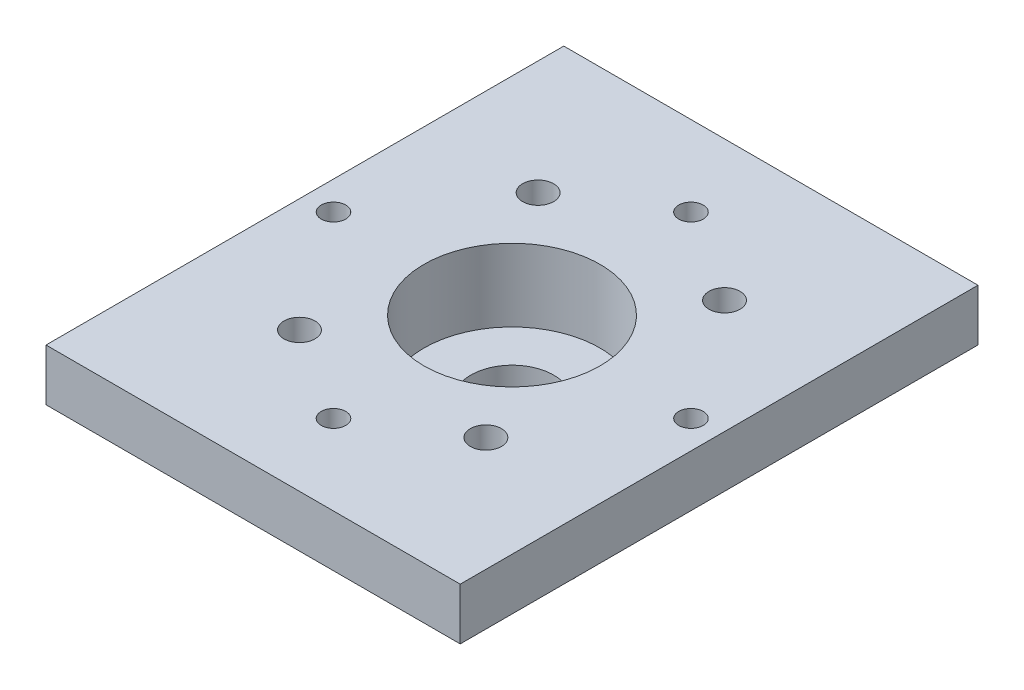
SolidWorks part; units mm, degrees
ref_plane "Front Plane" through (0, 0, 0) normal (0, 0, 1) x (1, 0, 0)
ref_plane "Top Plane" through (0, 0, 0) normal (0, 1, 0) x (1, 0, 0)
ref_plane "Right Plane" through (0, 0, 0) normal (1, 0, 0) x (0, 0, -1)
sketch "Sketch1" plane through (0, 0, 0) normal (0, 1, 0) x (1, 0, 0)
  line L0 (25.7342, 28.651) -> (-19.9858, -29.769) construction
  line L1 (-19.9858, 28.651) -> (25.7342, 28.651)
  line L2 (-19.9858, 28.651) -> (-19.9858, -29.769)
  line L3 (-19.9858, -29.769) -> (25.7342, -29.769)
  line L4 (25.7342, 28.651) -> (25.7342, -29.769)
  point P4 (2.8742, -0.559)
  point P5 (0, 0)
  dimension "D1" = 58.42
  dimension "D2" = 45.72
extrude "Boss-Extrude1" add sketch "Sketch1" along normal blind 6.35
sketch "Sketch2" plane through (0, 6.35, 0) normal (0, 1, 0) x (1, 0, 0)
  line L1 (25.7342, 28.651) -> (-19.9858, 28.651) construction
  line L3 (-19.9858, -0.559) -> (25.7342, -0.559) construction
  line L4 (-19.9858, 28.651) -> (-19.9858, -29.769) construction
  line L5 (25.7342, -29.769) -> (25.7342, 28.651) construction
  line L9 (-19.9858, -0.559) -> (2.8742, 28.651) construction
  line L10 (2.8742, 28.651) -> (25.7342, -0.559) construction
  circle A0 centre (-8.5558, 14.046) radius 1.905
  circle A1 centre (14.3042, 14.046) radius 1.905
  circle A2 centre (-8.6123, -15.164) radius 1.905
  circle A3 centre (14.2477, -15.164) radius 1.905
  dimension "D2" = 3.81
  dimension "D3" = 3.81
  dimension "D4" = 3.81
  dimension "D5" = 3.81
  dimension "D1" = 18.5459
  dimension "D6" = 29.21
  dimension "D7" = 29.21
  dimension "D8" = 22.86
  dimension "D9" = 22.86
sketch "Sketch3" plane through (0, 0, 0) normal (0, -1, 0) x (1, 0, 0)
  line L1 (-15.4979, 23.6108) -> (21.2464, 23.6108)
  line L2 (-15.4979, 23.6108) -> (-15.4979, -22.4927)
  line L3 (-15.4979, -22.4927) -> (21.2464, -22.4927)
  line L4 (21.2464, 23.6108) -> (21.2464, -22.4927)
  dimension "D1" = 7.62
  dimension "D2" = 7.62
extrude "Cut-Extrude1" cut sketch "Sketch2" against normal through all
extrude "Boss-Extrude2" add sketch "Sketch3" along normal blind 5.08
sketch "Sketch4" plane through (0, -5.08, 0) normal (0, -1, 0) x (1, 0, 0)
  line L0 (-19.9858, 0.559) -> (25.7342, 0.559) construction
  line L1 (-19.9858, -28.651) -> (-19.9858, 29.769) construction
  line L2 (25.7342, 29.769) -> (25.7342, -28.651) construction
  line L3 (2.8742, 29.769) -> (2.8742, -28.651) construction
  line L4 (-19.9858, 29.769) -> (25.7342, 29.769) construction
  line L5 (25.7342, -28.651) -> (-19.9858, -28.651) construction
  circle A0 centre (2.8742, 0.559) radius 7.62
  circle A1 centre (2.8742, 0.559) radius 5.08
  dimension "D1" = 10.16
  dimension "D2" = 15.24
extrude "Boss-Extrude3" add sketch "Sketch4" along normal blind 12.7
fillet "Fillet1" radius 2.54 4 edges at (25.7342, 3.175, -28.651) (-19.9858, 3.175, -28.651) (-19.9858, 3.175, 29.769) (25.7342, 3.175, 29.769)
sketch "Sketch5" plane through (0, 6.35, 0) normal (0, 1, 0) x (1, 0, 0)
  line L0 (-8.5558, 14.046) -> (14.2477, -15.164) construction
  circle A0 centre (2.846, -0.559) radius 10.795
  point P7 (2.846, -0.559)
  dimension "D1" = 21.59
extrude "Cut-Extrude2" cut sketch "Sketch5" against normal blind 8.89
extrude "Cut-Extrude4" cut sketch "Sketch4<2>" against normal blind 19.05 contours A1 region at (2.8742, -5.08, 0.559)
sketch "Sketch4<2>" plane through (0, -5.08, 0) normal (0, -1, 0) x (1, 0, 0) same geometry as "Sketch4"
sketch "Sketch6" plane through (0, 6.35, 0) normal (0, 1, 0) x (1, 0, 0)
  line L1 (28.246, 31.191) -> (-22.554, 31.191)
  line L2 (28.246, 31.191) -> (28.246, -32.309)
  line L3 (28.246, -32.309) -> (-22.554, -32.309)
  line L4 (-22.554, 31.191) -> (-22.554, -32.309)
  line L5 (28.246, 31.191) -> (-22.554, -32.309) construction
  line L6 (28.246, -32.309) -> (-22.554, 31.191) construction
  line L7 (22.0009, 23.3846) -> (-16.3089, 23.3846)
  line L8 (22.0009, 23.3846) -> (22.0009, -24.5026)
  line L9 (22.0009, -24.5026) -> (-16.3089, -24.5026)
  line L10 (-16.3089, 23.3846) -> (-16.3089, -24.5026)
  line L11 (22.0009, 23.3846) -> (-16.3089, -24.5026) construction
  line L12 (22.0009, -24.5026) -> (-16.3089, 23.3846) construction
  point P0 (2.846, -0.559)
  point P6 (2.846, -0.559)
  line M8 (25.7342, -27.229) -> (25.7342, 26.111)
  arc M9 (25.7342, 26.111) -> (23.1942, 28.651) centre (23.1942, 26.111) ccw
  line M10 (23.1942, 28.651) -> (-17.4458, 28.651)
  arc M11 (-17.4458, 28.651) -> (-19.9858, 26.111) centre (-17.4458, 26.111) ccw
  line M12 (-19.9858, 26.111) -> (-19.9858, -27.229)
  arc M13 (-19.9858, -27.229) -> (-17.4458, -29.769) centre (-17.4458, -27.229) ccw
  line M14 (-17.4458, -29.769) -> (23.1942, -29.769)
  arc M15 (23.1942, -29.769) -> (25.7342, -27.229) centre (23.1942, -27.229) ccw
  dimension "D1" = 50.8
  dimension "D2" = 63.5
extrude "Boss-Extrude4" add sketch "Sketch6" along direction (0, 1, 0) on the side against the normal blind 6.35 contours L1 L4 L3 L2 M8 M15 M14 M13 M12 M11 M10 M9 | L10 L7 L8 L9 M15 M8 M9 M10 M11 M12 M13 M14 region at (27.4328, 6.35, 0.559) region at (24.4657, 6.35, 28.5005)
sketch "Sketch7" plane through (0, 6.35, 0) normal (0, 1, 0) x (1, 0, 0)
  line L0 (2.8742, 21.3613) -> (2.8742, -22.4794) construction
  line L1 (2.8742, -22.4794) -> (24.7945, -0.559) construction
  line L2 (24.7945, -0.559) -> (2.8742, 21.3613) construction
  line L3 (2.8742, 21.3613) -> (-19.0461, -0.559) construction
  line L4 (-19.0461, -0.559) -> (2.8742, -22.4794) construction
  circle A0 centre (2.8742, 21.3613) radius 1.5
  circle A1 centre (2.8742, -22.4794) radius 1.5
  circle A2 centre (-19.0461, -0.559) radius 1.5
  circle A3 centre (24.7945, -0.559) radius 1.5
  circle A4 centre (2.8742, -0.559) radius 5.08 construction
  point P4 (2.8742, -0.559)
  point P9 (2.9005, -1.1806)
  dimension "D2" = 3
  dimension "D1" = 90
  dimension "D3" = 31
extrude "Cut-Extrude5" cut sketch "Sketch7" against normal through all
